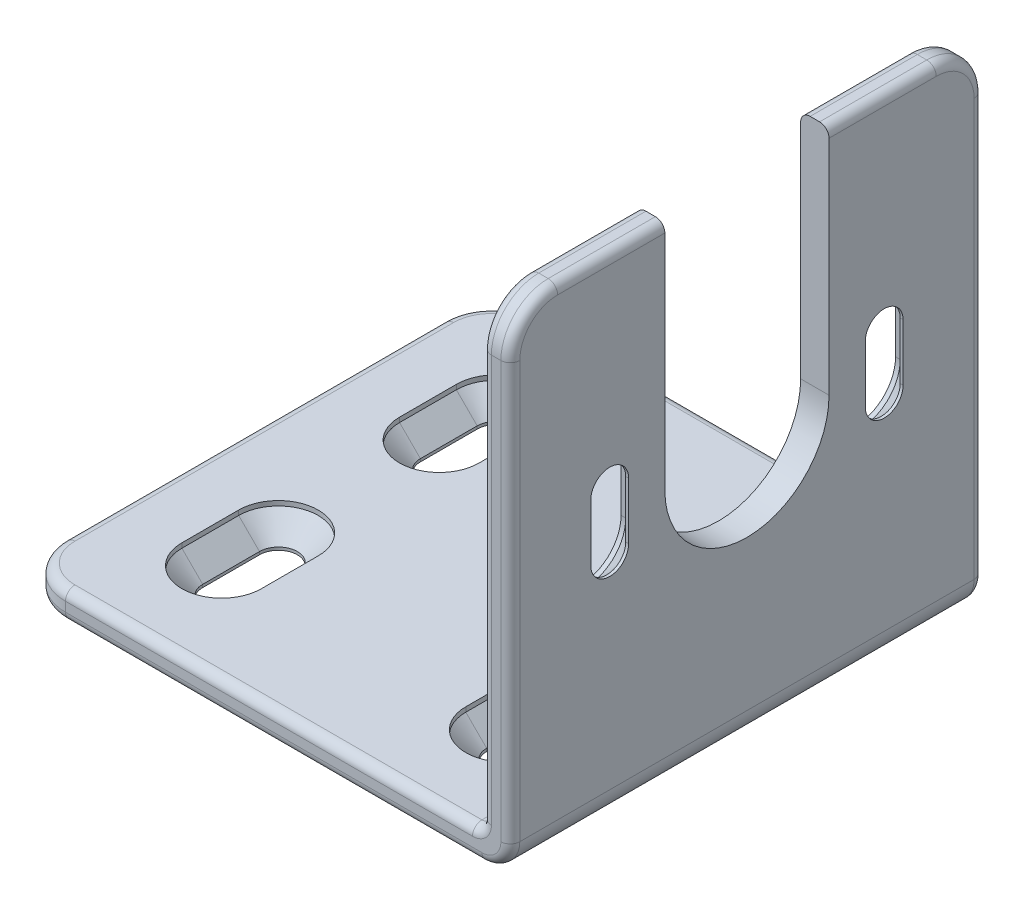
SolidWorks part; units mm, degrees
ref_plane "Front Plane" through (0, 0, 0) normal (0, 0, 1) x (1, 0, 0)
ref_plane "Top Plane" through (0, 0, 0) normal (0, 1, 0) x (1, 0, 0)
ref_plane "Right Plane" through (0, 0, 0) normal (1, 0, 0) x (0, 0, -1)
sketch "Sketch1" plane through (0, 0, 0) normal (0, 1, 0) x (1, 0, 0)
  line L0 (-15, 14.5) -> (-15, 8.5) construction
  line L1 (-21, -25) -> (26, -25)
  line L2 (-26, -20) -> (-26, 20)
  line L3 (-21, 25) -> (26, 25)
  line L4 (26, -25) -> (26, 25)
  line L5 (-26, -25) -> (26, 25) construction
  line L6 (-26, 25) -> (26, -25) construction
  line L7 (-13, 14.5) -> (-13, 8.5)
  line L8 (-17, 14.5) -> (-17, 8.5)
  line L9 (-26, 0) -> (26, 0) construction
  line L10 (0, 25) -> (0, -25) construction
  line L11 (15, 14.5) -> (15, 8.5) construction
  line L12 (13, 14.5) -> (13, 8.5)
  line L13 (17, 14.5) -> (17, 8.5)
  line L14 (15, -14.5) -> (15, -8.5) construction
  line L15 (13, -14.5) -> (13, -8.5)
  line L16 (17, -14.5) -> (17, -8.5)
  line L17 (-15, -14.5) -> (-15, -8.5) construction
  line L18 (-13, -14.5) -> (-13, -8.5)
  line L19 (-17, -14.5) -> (-17, -8.5)
  arc A0 (-21, -25) -> (-26, -20) centre (-21, -20) cw
  arc A1 (-26, 20) -> (-21, 25) centre (-21, 20) cw
  arc A2 (-13, 14.5) -> (-17, 14.5) centre (-15, 14.5) ccw
  arc A3 (-17, 8.5) -> (-13, 8.5) centre (-15, 8.5) ccw
  arc A4 (13, 14.5) -> (17, 14.5) centre (15, 14.5) cw
  arc A5 (17, 8.5) -> (13, 8.5) centre (15, 8.5) cw
  arc A6 (13, -14.5) -> (17, -14.5) centre (15, -14.5) ccw
  arc A7 (17, -8.5) -> (13, -8.5) centre (15, -8.5) ccw
  arc A8 (-13, -14.5) -> (-17, -14.5) centre (-15, -14.5) cw
  arc A9 (-17, -8.5) -> (-13, -8.5) centre (-15, -8.5) cw
  point P0 (0, 0)
  point P14 (-15, 11.5)
  point P19 (-15, 6.5)
  point P26 (15, 11.5)
  point P33 (15, -11.5)
  point P41 (-15, -11.5)
  point P46 (-15, 16.5)
  dimension "D3" = 5
  dimension "D1" = 4
  dimension "D2" = 52
  dimension "D4" = 13.5
  dimension "D5" = 11
  dimension "D6" = 10
extrude "Boss-Extrude1" add sketch "Sketch1" along normal blind 3
ref_plane "Plane1" through (26, 0, 0) normal (1, 0, 0) x (0, 0, -1)
sketch "Sketch2" plane through (26, 0, 0) normal (1, 0, 0) x (0, 0, -1)
  line L0 (-14.5, 24.515) -> (-14.5, 30.515) construction
  line L1 (25, 3) -> (-25, 3)
  line L2 (25, 3) -> (25, 47.03)
  line L3 (20, 52.03) -> (8.675, 52.03)
  line L4 (-25, 3) -> (-25, 47.03)
  line L5 (25, 3) -> (-25, 52.03) construction
  line L6 (25, 52.03) -> (-25, 3) construction
  line L7 (-16.5, 24.515) -> (-16.5, 30.515)
  line L8 (-12.5, 24.515) -> (-12.5, 30.515)
  line L9 (14.5, 30.515) -> (14.5, 24.515) construction
  line L10 (-25, 3) -> (25, 3) construction
  line L11 (-8.675, 27.515) -> (-8.675, 52.03)
  line L12 (8.675, 27.515) -> (8.675, 52.03)
  line L13 (-8.675, 52.03) -> (-20, 52.03)
  line L14 (16.5, 30.515) -> (16.5, 24.515)
  line L15 (12.5, 30.515) -> (12.5, 24.515)
  line L16 (-14.5, 27.515) -> (0, 27.515) construction
  line L17 (0, 27.515) -> (14.5, 27.515) construction
  arc A0 (25, 47.03) -> (20, 52.03) centre (20, 47.03) ccw
  arc A1 (-20, 52.03) -> (-25, 47.03) centre (-20, 47.03) ccw
  arc A2 (-8.675, 27.515) -> (8.675, 27.515) centre (0, 27.515) ccw
  arc A3 (-16.5, 24.515) -> (-12.5, 24.515) centre (-14.5, 24.515) ccw
  arc A4 (-12.5, 30.515) -> (-16.5, 30.515) centre (-14.5, 30.515) ccw
  arc A5 (16.5, 30.515) -> (12.5, 30.515) centre (14.5, 30.515) ccw
  arc A6 (12.5, 24.515) -> (16.5, 24.515) centre (14.5, 24.515) ccw
  point P0 (0, 27.515)
  point P21 (-14.5, 27.515)
  point P26 (14.5, 27.515)
  point P34 (-14.5, 32.515)
  point P36 (-14.5, 22.515)
  dimension "D1" = 5
  dimension "D3" = 17.35
  dimension "D6" = 10
  dimension "D2" = 49.03
  dimension "D4" = 29
  dimension "D5" = 4
extrude "Boss-Extrude3" add sketch "Sketch2" against normal blind 3
fillet "Fillet2" radius 3 1 edges at (26, 0, 0)
fillet "Fillet4" radius 1 1 edges at (23, 3, 0)
fillet "Fillet5" radius 1 26 edges at (23, 52.03, -14.3375) (23, 50.5655, -23.5355) (23, 25.515, -25) (22.7071, 3.2929, -25) (0.5, 3, -25) (-24.5355, 3, -23.5355) (-26, 3, 0) (-24.5355, 3, 23.5355) (23, 52.03, 14.3375) (23, 50.5655, 23.5355) (22.7071, 3.2929, 25) (26, 52.03, 14.3375) (26, 50.5655, 23.5355) (26, 52.03, -14.3375) (26, 50.5655, -23.5355) (26, 25.015, -25) (25.1213, 0.8787, -25) (1, 0, -25) (-24.5355, 0, -23.5355) (-26, 0, 0) (-24.5355, 0, 23.5355) (25.1213, 0.8787, 25) (23, 25.515, 25) (0.5, 3, 25) (1, 0, 25) (26, 25.015, 25)
sketch "Sketch5" plane through (0, 3, 0) normal (0, 1, 0) x (1, 0, 0)
  line L0 (-15, 8.5) -> (-15, 14.5) construction
  line L1 (-19.2, 8.5) -> (-19.2, 14.5)
  line L2 (-10.8, 8.5) -> (-10.8, 14.5)
  line L3 (0, 25) -> (0, -25) construction
  line L4 (-26, 0) -> (26, 0) construction
  line L5 (15, 8.5) -> (15, 14.5) construction
  line L6 (19.2, 8.5) -> (19.2, 14.5)
  line L7 (10.8, 8.5) -> (10.8, 14.5)
  line L8 (-15, -8.5) -> (-15, -14.5) construction
  line L9 (-19.2, -8.5) -> (-19.2, -14.5)
  line L10 (-10.8, -8.5) -> (-10.8, -14.5)
  line L11 (15, -8.5) -> (15, -14.5) construction
  line L12 (19.2, -8.5) -> (19.2, -14.5)
  line L13 (10.8, -8.5) -> (10.8, -14.5)
  arc A0 (-19.2, 8.5) -> (-10.8, 8.5) centre (-15, 8.5) ccw
  arc A1 (-10.8, 14.5) -> (-19.2, 14.5) centre (-15, 14.5) ccw
  arc A2 (19.2, 8.5) -> (10.8, 8.5) centre (15, 8.5) cw
  arc A3 (10.8, 14.5) -> (19.2, 14.5) centre (15, 14.5) cw
  arc A4 (-19.2, -8.5) -> (-10.8, -8.5) centre (-15, -8.5) cw
  arc A5 (-10.8, -14.5) -> (-19.2, -14.5) centre (-15, -14.5) cw
  arc A6 (19.2, -8.5) -> (10.8, -8.5) centre (15, -8.5) ccw
  arc A7 (10.8, -14.5) -> (19.2, -14.5) centre (15, -14.5) ccw
  point P4 (-15, 11.5)
  point P19 (15, 11.5)
  point P26 (-15, -11.5)
  point P33 (15, -11.5)
  dimension "D1" = 8.4
extrude "Cut-Extrude4" cut sketch "Sketch5" against normal blind 0.5
sketch "Sketch6" plane through (23, 0, 0) normal (-1, 0, 0) x (0, 0, 1)
  line L0 (-14.5, 30.515) -> (-14.5, 24.515) construction
  line L1 (-10.3, 30.515) -> (-10.3, 24.515)
  line L2 (-18.7, 30.515) -> (-18.7, 24.515)
  line L4 (0, 52.03) -> (0, 3) construction
  line L5 (-25, 3) -> (25, 3) construction
  line L6 (14.5, 30.515) -> (14.5, 24.515) construction
  line L7 (10.3, 30.515) -> (10.3, 24.515)
  line L8 (18.7, 30.515) -> (18.7, 24.515)
  arc A0 (-10.3, 30.515) -> (-18.7, 30.515) centre (-14.5, 30.515) ccw
  arc A1 (-18.7, 24.515) -> (-10.3, 24.515) centre (-14.5, 24.515) ccw
  arc A2 (10.3, 30.515) -> (18.7, 30.515) centre (14.5, 30.515) cw
  arc A3 (18.7, 24.515) -> (10.3, 24.515) centre (14.5, 24.515) cw
  point P4 (-14.5, 27.515)
  point P19 (14.5, 27.515)
  dimension "D1" = 8.4
extrude "Cut-Extrude8" cut sketch "Sketch6" against normal blind 0.5
sketch "Sketch7" plane through (17, 0, 0) normal (-1, 0, 0) x (0, 0, 1)
  line L0 (-14.5, 0.3) -> (-8.5, 0.3) construction
  line L4 (-8.5, 2.5) -> (-14.5, 2.5)
  line L5 (-14.5, 2.5) -> (-14.5, 0)
  line L7 (-8.5, 0) -> (-8.5, 2.5)
  line L9 (-14.5, 2.5) -> (-14.5, 0)
  line L11 (-8.5, 0) -> (-8.5, 2.5)
  line L13 (-8.5, 2.5) -> (-14.5, 2.5)
  line L15 (-14.5, 0) -> (-8.5, 0)
  line L16 (-14.5, 0) -> (-8.5, 0)
  dimension "D2" = 0.3
  dimension "D1" = 0
ref_plane "Plane3" through (0, 0.3, 0) normal (0, 1, 0) x (1, 0, 0)
sketch "Sketch8" plane through (0, 0.3, 0) normal (0, 1, 0) x (1, 0, 0)
  line L0 (-15, 14.5) -> (-15, 8.5) construction
  line L1 (-13, 14.5) -> (-13, 8.5)
  line L2 (-17, 14.5) -> (-17, 8.5)
  line L3 (0, 25) -> (0, -25) construction
  line L4 (-26, 0) -> (26, 0) construction
  line L5 (15, 14.5) -> (15, 8.5) construction
  line L6 (13, 14.5) -> (13, 8.5)
  line L7 (17, 14.5) -> (17, 8.5)
  line L8 (-15, -14.5) -> (-15, -8.5) construction
  line L9 (-13, -14.5) -> (-13, -8.5)
  line L10 (-17, -14.5) -> (-17, -8.5)
  line L11 (15, -14.5) -> (15, -8.5) construction
  line L12 (13, -14.5) -> (13, -8.5)
  line L13 (17, -14.5) -> (17, -8.5)
  arc A0 (-13, 14.5) -> (-17, 14.5) centre (-15, 14.5) ccw
  arc A1 (-17, 8.5) -> (-13, 8.5) centre (-15, 8.5) ccw
  arc A2 (-13, 14.5) -> (-17, 14.5) centre (-15, 14.5) ccw construction
  arc A3 (13, 14.5) -> (17, 14.5) centre (15, 14.5) cw
  arc A4 (17, 8.5) -> (13, 8.5) centre (15, 8.5) cw
  arc A5 (-13, -14.5) -> (-17, -14.5) centre (-15, -14.5) cw
  arc A6 (-17, -8.5) -> (-13, -8.5) centre (-15, -8.5) cw
  arc A7 (13, -14.5) -> (17, -14.5) centre (15, -14.5) ccw
  arc A8 (17, -8.5) -> (13, -8.5) centre (15, -8.5) ccw
  point P4 (-15, 11.5)
  point P22 (15, 11.5)
  point P29 (-15, -11.5)
  point P36 (15, -11.5)
extrude "Cut-Extrude11" cut sketch "Sketch8" along normal up to vertex (2.2 mm away) draft 45 up to point (19.2, 2.5, -14.5) draft outward yes
sketch "Sketch15" plane through (0, 0, 16.5) normal (0, 0, -1) x (-1, 0, 0)
  line L0 (-23.5, 30.515) -> (-26, 30.515) construction
  line L1 (-25.6923, 30.515) -> (-25.6923, 24.515) construction
  line L2 (-23.5, 24.515) -> (-26, 24.515) construction
ref_plane "Plane5" through (25.6923, 0, 0) normal (1, 0, 0) x (0, 0, -1)
sketch "Sketch16" plane through (25.6923, 0, 0) normal (1, 0, 0) x (0, 0, -1)
  line L0 (14.5, 30.515) -> (14.5, 24.515) construction
  line L1 (16.5, 30.515) -> (16.5, 24.515)
  line L2 (12.5, 30.515) -> (12.5, 24.515)
  line L3 (-14.5, 30.515) -> (-14.5, 24.515) construction
  line L4 (-12.5, 30.515) -> (-12.5, 24.515)
  line L5 (-16.5, 30.515) -> (-16.5, 24.515)
  arc A0 (16.5, 30.515) -> (12.5, 30.515) centre (14.5, 30.515) ccw
  arc A1 (12.5, 24.515) -> (16.5, 24.515) centre (14.5, 24.515) ccw
  arc A2 (16.5, 30.515) -> (12.5, 30.515) centre (14.5, 30.515) ccw construction
  arc A3 (-12.5, 30.515) -> (-16.5, 30.515) centre (-14.5, 30.515) ccw
  arc A4 (-16.5, 24.515) -> (-12.5, 24.515) centre (-14.5, 24.515) ccw
  point P4 (14.5, 27.515)
  point P12 (-14.5, 27.515)
  point P20 (-14.5, 32.515)
  point P21 (-14.5, 22.515)
  dimension "D1" = 4
  dimension "D2" = 10
ref_plane "Plane6" through (19.2, 3, -14.5) normal (0, 0, -1) x (-1, 0, 0)
extrude "Cut-Extrude12" cut sketch "Sketch16" against normal up to vertex (2.1923 mm away) draft 45 up to point (23.5, 30.515, -10.3) draft outward yes
